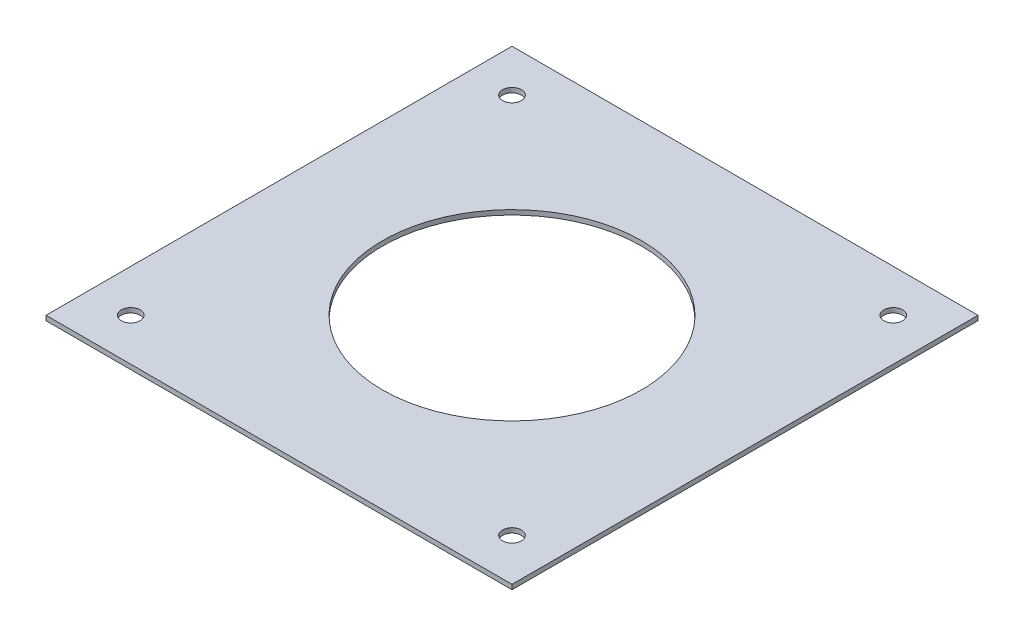
SolidWorks part; units mm, degrees
ref_plane "Front Plane" through (0, 0, 0) normal (0, 0, 1) x (1, 0, 0)
ref_plane "Top Plane" through (0, 0, 0) normal (0, 1, 0) x (1, 0, 0)
ref_plane "Right Plane" through (0, 0, 0) normal (1, 0, 0) x (0, 0, -1)
sketch "Sketch1" plane through (0, 0, 0) normal (0, 1, 0) x (1, 0, 0)
  line L1 (-49.3914, -49.3914) -> (49.3914, -49.3914)
  line L2 (-49.3914, -49.3914) -> (-49.3914, 49.3914)
  line L3 (-49.3914, 49.3914) -> (49.3914, 49.3914)
  line L4 (49.3914, -49.3914) -> (49.3914, 49.3914)
  line L5 (-49.3914, -49.3914) -> (49.3914, 49.3914) construction
  line L6 (-49.3914, 49.3914) -> (49.3914, -49.3914) construction
  point P0 (0, 0)
  dimension "D1" = 139.7
extrude "Boss-Extrude1" add sketch "Sketch1" along normal blind 1
sketch "Sketch3" plane through (0, 0, 0) normal (0, 1, 0) x (1, 0, 0)
  line L0 (-49.3914, -49.3914) -> (49.3914, 49.3914) construction
  line L1 (-40.4112, 40.4112) -> (40.4112, -40.4112) construction
  circle A0 centre (40.4112, 40.4112) radius 2
  circle A1 centre (40.4112, -40.4112) radius 2
  circle A2 centre (-40.4112, -40.4112) radius 2
  circle A3 centre (-40.4112, 40.4112) radius 2
  point P15 (0, 0)
  dimension "D3" = 4
  dimension "D2" = 114.3
  dimension "D1" = 4
extrude "Cut-Extrude2" cut sketch "Sketch3" along normal through all
sketch "Sketch8" plane through (0, 0, 0) normal (0, 1, 0) x (1, 0, 0)
  circle A0 centre (0, 0) radius 27.432 construction
  circle A1 centre (0, 0) radius 27.432
extrude "Cut-Extrude9" cut sketch "Sketch8" along normal through all
equation "\"D1@Boss-Extrude1\"=1mm"
equation "\"D3@Sketch3\"=4mm"
